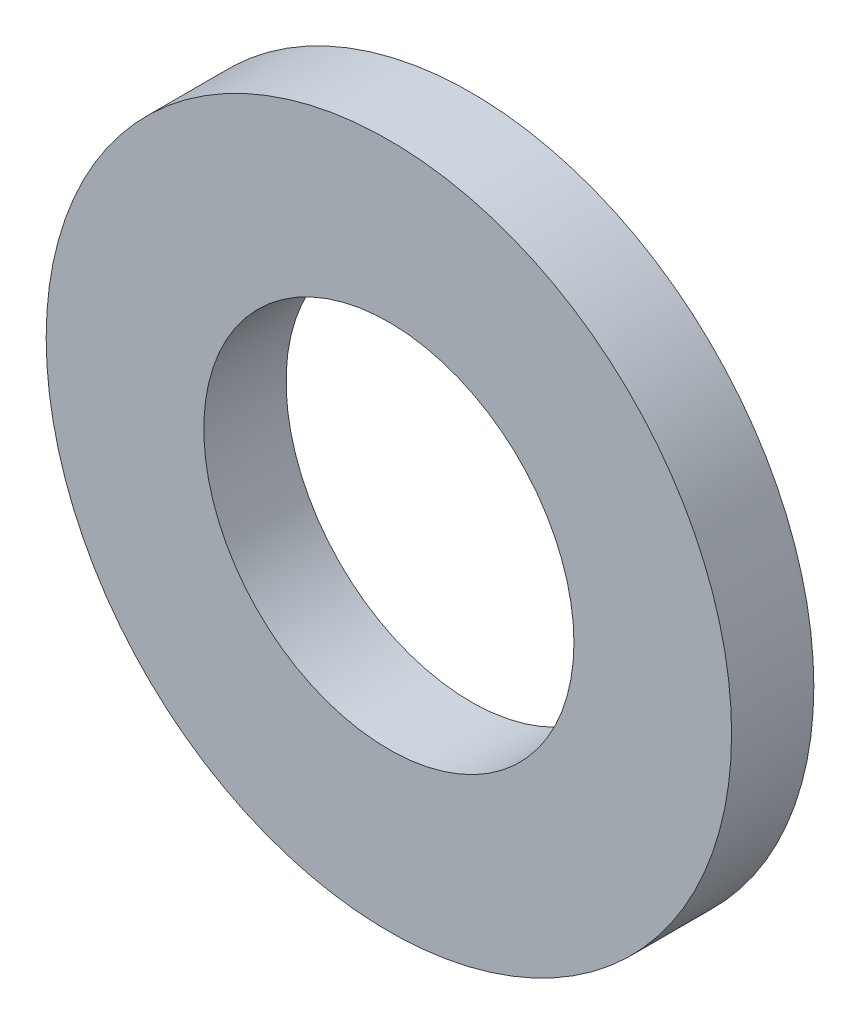
SolidWorks part; units mm, degrees
ref_plane "Front Plane" through (0, 0, 0) normal (0, 0, 1) x (1, 0, 0)
ref_plane "Top Plane" through (0, 0, 0) normal (0, 1, 0) x (1, 0, 0)
ref_plane "Right Plane" through (0, 0, 0) normal (1, 0, 0) x (0, 0, -1)
sketch "Sketch1" plane through (0, 0, 0) normal (0, 0, 1) x (1, 0, 0)
  circle A0 centre (0, 0) radius 2.5
  circle A1 centre (0, 0) radius 1.35
  dimension "OD" = 5
  dimension "ID1" = 2.7
extrude "Boss-Extrude1" add sketch "Sketch1" along normal blind 0.6
ref_axis "Center Axis 1" through (0, 0, 0.6) along (0, 0, -1)
ref_plane "Contact Plane 1" through (0, 0, 0.6) normal (0, 0, 1) x (1, 0, 0)
ref_plane "Contact Plane 2" through (0, 0, 0) normal (0, 0, -1) x (-1, 0, 0)
